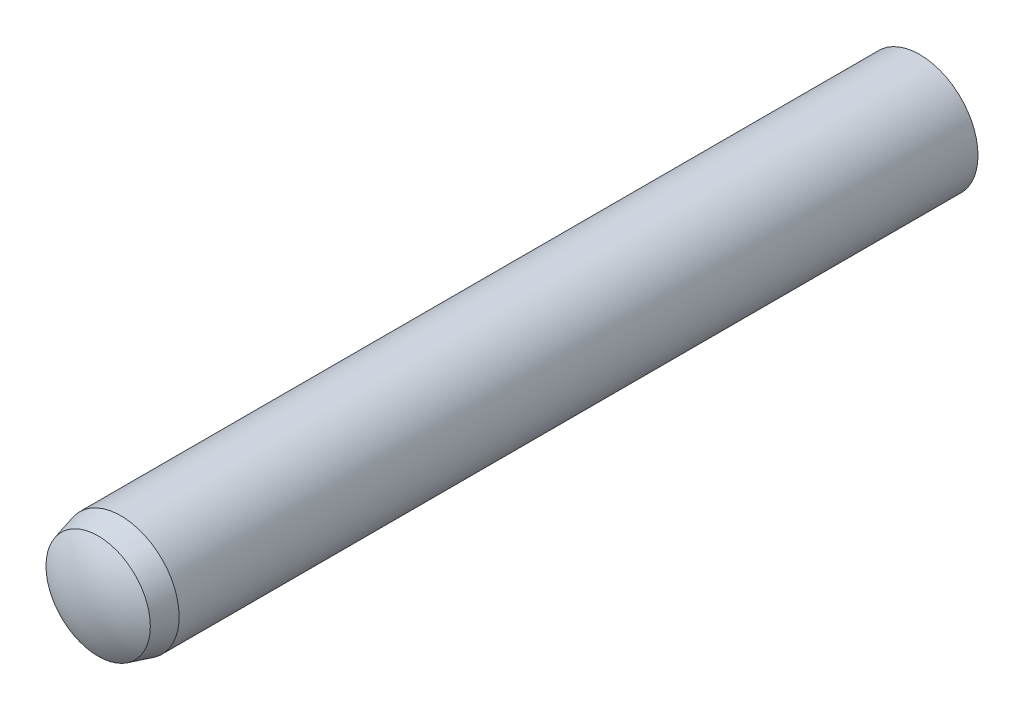
SolidWorks part; units mm, degrees
ref_plane "Front Plane" through (0, 0, 0) normal (0, 0, 1) x (1, 0, 0)
ref_plane "Top Plane" through (0, 0, 0) normal (0, 1, 0) x (1, 0, 0)
ref_plane "Right Plane" through (0, 0, 0) normal (1, 0, 0) x (0, 0, -1)
sketch "Sketch1" plane through (0, 0, 0) normal (0, 0, 1) x (1, 0, 0)
  circle A0 centre (0, 0) radius 1.5
  point P3 (0, 1.5)
  dimension "Diameter" = 3
sketch "Sketch2" plane through (0, 0, 0) normal (1, 0, 0) x (0, 0, -1)
  line L0 (-11, 0) -> (11, 0) construction
  line L1 (-11, 0) -> (-11, 1.5) construction
  line L2 (-11, 1.5) -> (11, 1.5)
  line L3 (11, 1.5) -> (11, 0) construction
  line L4 (-10.61, 1.3432) -> (-10.025, 1.5)
  arc A0 (-11, 0) -> (-10.61, 1.3432) centre (-8.4918, 0) cw
  arc A1 (11, 0) -> (10.55, 1.5) centre (8.275, 0) ccw
  point P2 (0, 0)
  point P11 (-8, 0)
  point P13 (8, 0)
  dimension "D1" = 15
  dimension "D2" = 0.45
  dimension "D3" = 0.975
  dimension "D4" = 0.585
  dimension "D5" = 3
  dimension "D6" = 3
sketch "Sketch3" plane through (0, 0, 0) normal (1, 0, 0) x (0, 0, -1)
  line L0 (-11, 0) -> (11, 0) construction
  line L1 (-10.61, 1.3432) -> (-10.025, 1.5) construction
  line L2 (-11, 0) -> (11, 0)
  line L3 (-10.61, 1.3432) -> (-10.025, 1.5)
  line L4 (-10.025, 1.5) -> (10.55, 1.5)
  arc A0 (11, 0) -> (10.55, 1.5) centre (8.275, 0) ccw construction
  arc A1 (-10.61, 1.3432) -> (-11, 0) centre (-8.4918, 0) ccw construction
  arc A2 (11, 0) -> (10.55, 1.5) centre (8.275, 0) ccw
  arc A3 (-10.61, 1.3432) -> (-11, 0) centre (-8.4918, 0) ccw
revolve "Revolve1" add sketch "Sketch3" angle 360 about L2
ref_plane "Plane1" through (0, 0, 11) normal (0, 0, 1) x (1, 0, 0)
equation "\"D2@Sketch2\" = \"Diameter@Sketch1\" * .15"
equation "\"D3@Sketch2\" = \"Diameter@Sketch1\" * .325"
equation "\"D4@Sketch2\" = \"D3@Sketch2\" * .6"
equation "\"D5@Sketch2\"=\"Diameter@Sketch1\""
equation "\"D6@Sketch2\" = \"D5@Sketch2\""
